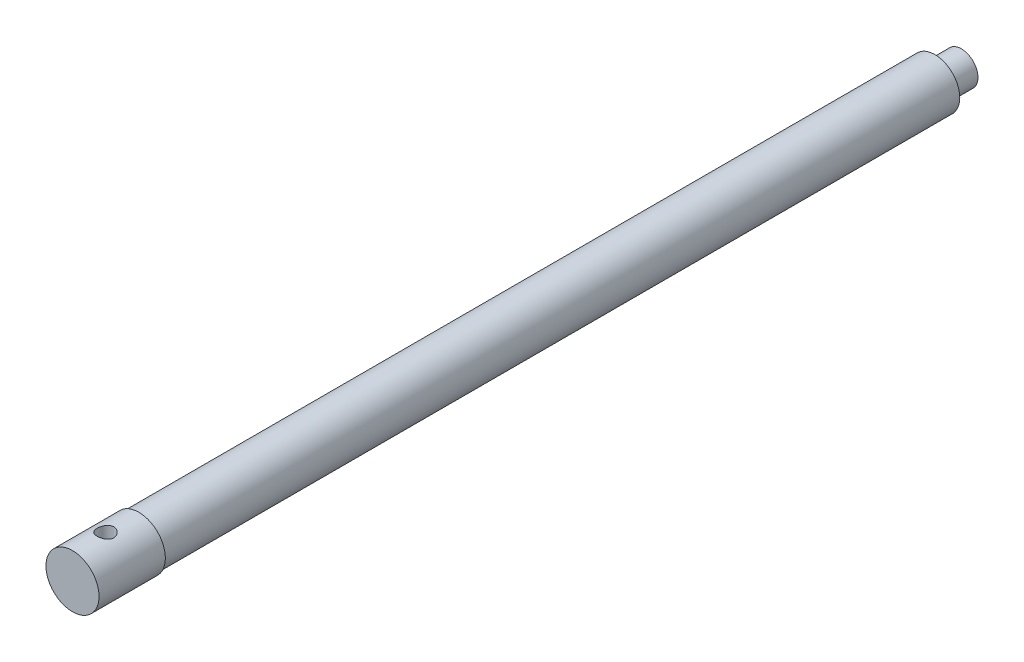
SolidWorks part; units mm, degrees
material "Stainless Steel (ferritic)"
ref_plane "Front Plane" through (0, 0, 0) normal (0, 0, 1) x (1, 0, 0)
ref_plane "Top Plane" through (0, 0, 0) normal (0, 1, 0) x (1, 0, 0)
ref_plane "Right Plane" through (0, 0, 0) normal (1, 0, 0) x (0, 0, -1)
sketch "Sketch1" plane through (0, 0, 0) normal (0, 0, 1) x (1, 0, 0)
  circle A0 centre (0, 0) radius 7.5
  dimension "D1" = 15
extrude "Boss-Extrude1" add sketch "Sketch1" along normal blind 240
cosmetic thread "Cosmetic Thread2" parameters "D2"=11.797
sketch "Sketch5" plane through (0, 0, 240) normal (0, 0, 1) x (1, 0, 0)
  circle A0 centre (0, 0) radius 8
  dimension "D1" = 16
extrude "Boss-Extrude2" add sketch "Sketch5" along normal blind 20
sketch "Sketch8" plane through (0, 0, 0) normal (0, 0, -1) x (-1, 0, 0)
  circle A0 centre (0, 0) radius 5
  dimension "D1" = 10
extrude "Boss-Extrude4" add sketch "Sketch8" along normal blind 8
sketch "Sketch9" plane through (0, 0, 0) normal (0, 1, 0) x (1, 0, 0)
  circle A0 centre (0, -250.0646) radius 2.5
  dimension "D1" = 5
extrude "Cut-Extrude3" cut sketch "Sketch9" against normal blind 8 and the other way blind 8
